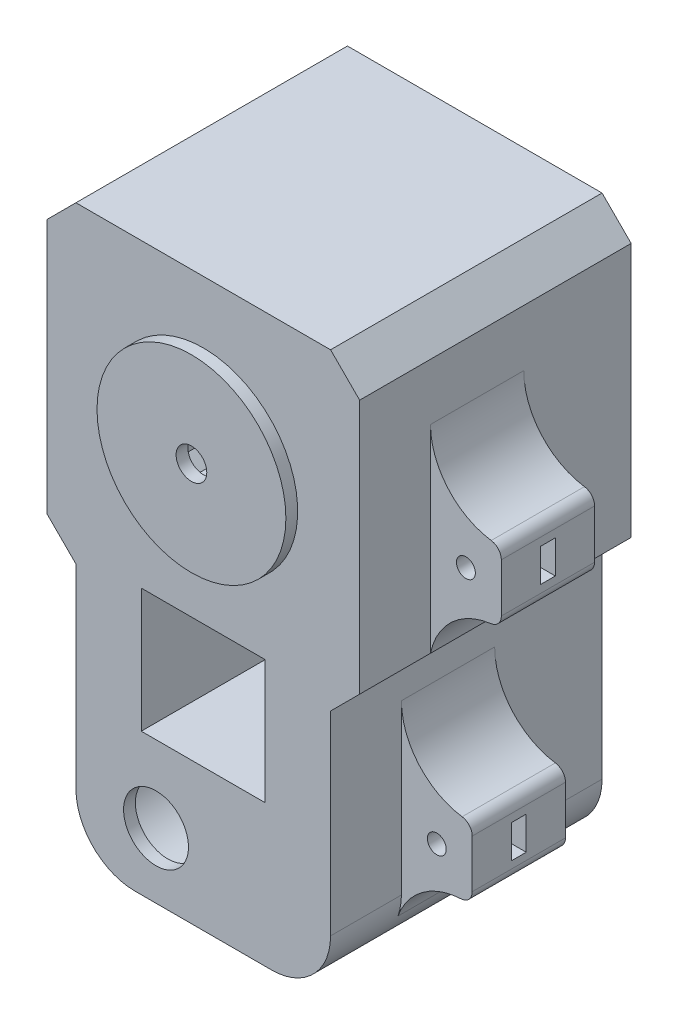
SolidWorks part; units mm, degrees
ref_plane "Alzado" through (0, 0, 0) normal (0, 0, 1) x (1, 0, 0)
ref_plane "Planta" through (0, 0, 0) normal (0, 1, 0) x (1, 0, 0)
ref_plane "Vista lateral" through (0, 0, 0) normal (1, 0, 0) x (0, 0, -1)
sketch "Croquis1" plane through (0, 0, 0) normal (0, 0, 1) x (1, 0, 0)
  line L0 (-19.5, -21.5) -> (-21.5, -19.5)
  line L1 (19.5, -21.5) -> (-19.5, -21.5)
  line L2 (21.5, -19.5) -> (21.5, 19.5)
  line L3 (19.5, 21.5) -> (-19.5, 21.5)
  line L4 (-21.5, -19.5) -> (-21.5, 19.5)
  line L5 (21.5, -21.5) -> (-21.5, 21.5) construction
  line L6 (21.5, 21.5) -> (-21.5, -21.5) construction
  line L7 (-19.5, 21.5) -> (-21.5, 19.5)
  line L8 (21.5, 19.5) -> (19.5, 21.5)
  line L9 (21.5, -19.5) -> (19.5, -21.5)
  line L10 (26.5, -21.5711) -> (26.5, 21.5711)
  line L11 (26.5, 21.5711) -> (21.5711, 26.5)
  line L12 (21.5711, 26.5) -> (-21.5711, 26.5)
  line L13 (-21.5711, 26.5) -> (-26.5, 21.5711)
  line L14 (-26.5, -21.5711) -> (-26.5, 21.5711)
  line L15 (-21.5711, -26.5) -> (-26.5, -21.5711)
  line L16 (21.5711, -26.5) -> (-21.5711, -26.5)
  line L17 (26.5, -21.5711) -> (21.5711, -26.5)
  point P0 (0, 0)
  dimension "D1" = 43
  dimension "D2" = 43
  dimension "D3" = 5
extrude "Saliente-Extruir1" add sketch "Croquis1" along normal mid plane 44
sketch "Croquis2" plane through (0, -26.5, 0) normal (0, -1, 0) x (1, 0, 0)
  line L4 (-21.5711, -22) -> (21.5711, -22)
  line L5 (21.5711, -22) -> (21.5711, 22)
  line L6 (21.5711, 22) -> (-21.5711, 22)
  line L7 (-21.5711, 22) -> (-21.5711, -22)
  line L8 (-21.5711, -22) -> (21.5711, -22)
  line L9 (21.5711, -22) -> (21.5711, 22)
  line L10 (21.5711, 22) -> (-21.5711, 22)
  line L11 (-21.5711, 22) -> (-21.5711, -22)
  dimension "D1" = 0
extrude "Saliente-Extruir2" add sketch "Croquis2" along normal blind 8
sketch "Croquis3" plane through (0, 0, 0) normal (0, 0, 1) x (1, 0, 0)
  line L0 (-19.5, -21.5) -> (19.5, -21.5) construction
  line L1 (-16.8806, -21.5) -> (16.8806, -21.5)
  line L2 (-16.8806, -21.5) -> (-16.8806, -29.5)
  line L3 (-16.8806, -29.5) -> (16.8806, -29.5)
  line L4 (16.8806, -21.5) -> (16.8806, -29.5)
  line L5 (0, 18.4155) -> (0, -35.026) construction
  dimension "D1" = 33.7612
  dimension "D2" = 8
extrude "Cortar-Extruir1" cut sketch "Croquis3" against normal through all contours L2 L1 L4 L3
sketch "Croquis4" plane through (0, 0, 22) normal (0, 0, -1) x (-1, 0, 0)
  line L10 (-26.5, -21.5711) -> (-21.5711, -26.5)
  line L11 (-21.5711, -26.5) -> (-21.5711, -34.5)
  line L12 (-21.5711, -34.5) -> (21.5711, -34.5)
  line L13 (21.5711, -34.5) -> (21.5711, -26.5)
  line L14 (21.5711, -26.5) -> (26.5, -21.5711)
  line L15 (26.5, -21.5711) -> (26.5, 21.5711)
  line L16 (26.5, 21.5711) -> (21.5711, 26.5)
  line L17 (21.5711, 26.5) -> (-21.5711, 26.5)
  line L18 (-21.5711, 26.5) -> (-26.5, 21.5711)
  line L19 (-26.5, 21.5711) -> (-26.5, -21.5711)
  line L20 (-26.5, -21.5711) -> (-21.5711, -26.5)
  line L21 (-21.5711, -26.5) -> (-21.5711, -34.5)
  line L22 (-21.5711, -34.5) -> (21.5711, -34.5)
  line L23 (21.5711, -34.5) -> (21.5711, -26.5)
  line L24 (21.5711, -26.5) -> (26.5, -21.5711)
  line L25 (26.5, -21.5711) -> (26.5, 21.5711)
  line L26 (26.5, 21.5711) -> (21.5711, 26.5)
  line L27 (21.5711, 26.5) -> (-21.5711, 26.5)
  line L28 (-21.5711, 26.5) -> (-26.5, 21.5711)
  line L29 (-26.5, 21.5711) -> (-26.5, -21.5711)
  circle A0 centre (0, 0) radius 11
  dimension "D2" = 22
  dimension "D1" = 0
extrude "Saliente-Extruir4" add sketch "Croquis4" against normal blind 2
sketch "Croquis7" plane through (0, 0, 24) normal (0, 0, 1) x (1, 0, 0)
  circle A0 centre (0, 0) radius 2.6
  circle A3 centre (0, 0) radius 16
  circle A4 centre (0, 0) radius 16
  dimension "D2" = 5.2
  dimension "D1" = 5
extrude "Saliente-Extruir5" add sketch "Croquis7" along normal blind 2
sketch "Croquis6" plane through (0, -29.5, 0) normal (0, 1, 0) x (1, 0, 0)
  line L0 (0, -24.5904) -> (0, 23.7869) construction
  line L1 (-14, 18) -> (14, 18)
  line L2 (-14, 18) -> (-14, 6)
  line L3 (-14, 6) -> (14, 6)
  line L4 (14, 18) -> (14, 6)
  dimension "D1" = 28
  dimension "D2" = 12
  dimension "D3" = 18
extrude "Cortar-Extruir3" cut sketch "Croquis6" against normal blind 13
sketch "Croquis8" plane through (0, 0, 0) normal (0, 0, 1) x (1, 0, 0)
  line L0 (-26.5, -21.5711) -> (-26.5, 21.5711)
  line L1 (-26.5, -21.5711) -> (-26.5, 21.5711)
  line L2 (-26.5, 21.5711) -> (-21.5711, 26.5)
  line L3 (-26.5, 21.5711) -> (-21.5711, 26.5)
  line L4 (-21.5711, 26.5) -> (21.5711, 26.5)
  line L5 (-21.5711, 26.5) -> (21.5711, 26.5)
  line L6 (21.5711, 26.5) -> (26.5, 21.5711)
  line L7 (21.5711, 26.5) -> (26.5, 21.5711)
  line L8 (26.5, 21.5711) -> (26.5, -21.5711)
  line L9 (26.5, 21.5711) -> (26.5, -21.5711)
  line L10 (26.5, -21.5711) -> (21.5711, -26.5)
  line L11 (26.5, -21.5711) -> (21.5711, -26.5)
  line L12 (21.5711, -26.5) -> (21.5711, -34.5)
  line L13 (21.5711, -26.5) -> (21.5711, -34.5)
  line L14 (21.5711, -34.5) -> (-21.5711, -34.5)
  line L15 (21.5711, -34.5) -> (-21.5711, -34.5)
  line L16 (-21.5711, -34.5) -> (-21.5711, -26.5)
  line L17 (-21.5711, -34.5) -> (-21.5711, -26.5)
  line L18 (-21.5711, -26.5) -> (-26.5, -21.5711)
  line L19 (-21.5711, -26.5) -> (-26.5, -21.5711)
  line L20 (0, 0) -> (-39.949, 0) construction
  line L21 (0, 0) -> (0, 31.7363) construction
  line L22 (26.5, -12) -> (38.5, -12)
  line L23 (-26.5, 0) -> (-38.5, 0)
  line L24 (-26.5, 0) -> (-26.5, -12)
  line L25 (-26.5, -12) -> (-38.5, -12)
  line L26 (-38.5, 0) -> (-38.5, -12)
  line L27 (38.5, 0) -> (38.5, -12)
  line L28 (26.5, 0) -> (38.5, 0)
  line L29 (26.5, 0) -> (26.5, -12)
  line L30 (-38.5, -12) -> (-26.5, 0) construction
  circle A0 centre (-32.5, -6) radius 1.6
  circle A1 centre (32.5, -6) radius 1.6
  dimension "D3" = 3.2
  dimension "D1" = 12
  dimension "D2" = 12
extrude "Saliente-Extruir6" add sketch "Croquis8" along normal blind 12 and the other way blind 3.8 contours L23 L26 L25 L1 | L28 L9 L22 L27 region at (-32.5, -11.8303, 0) region at (26.6697, -6, 0)
sketch "Croquis9" plane through (38.5, 0, 0) normal (1, 0, 0) x (0, 0, -1)
  line L0 (3.8, -6) -> (-12, -6) construction
  line L1 (3.8, 0) -> (3.8, -12) construction
  line L2 (-12, 0) -> (-12, -12) construction
  line L4 (-2.85, -3.2) -> (-5.35, -3.2)
  line L5 (-2.85, -3.2) -> (-2.85, -8.8)
  line L6 (-2.85, -8.8) -> (-5.35, -8.8)
  line L7 (-5.35, -3.2) -> (-5.35, -8.8)
  line L8 (-2.85, -3.2) -> (-5.35, -8.8) construction
  line L9 (-2.85, -8.8) -> (-5.35, -3.2) construction
  point P6 (-4.1, -6)
  dimension "D1" = 5.6
  dimension "D2" = 2.5
extrude "Cortar-Extruir4" cut sketch "Croquis9" against normal blind 10
mirror "Simetría1" about plane through (0, 0, 0) normal (1, 0, 0) of "Cortar-Extruir4"
sketch "Croquis11" plane through (0, -34.5, 0) normal (0, -1, 0) x (1, 0, 0)
  line L4 (-21.5711, 24) -> (-21.5711, -22)
  line L5 (-21.5711, -22) -> (21.5711, -22)
  line L6 (21.5711, -22) -> (21.5711, 24)
  line L7 (21.5711, 24) -> (-21.5711, 24)
  line L8 (-21.5711, 24) -> (-21.5711, -22)
  line L9 (-21.5711, -22) -> (21.5711, -22)
  line L10 (21.5711, -22) -> (21.5711, 24)
  line L11 (21.5711, 24) -> (-21.5711, 24)
  dimension "D1" = 0
extrude "Saliente-Extruir8" add sketch "Croquis11" along normal blind 35
sketch "Croquis12" plane through (0, 0, -22) normal (0, 0, -1) x (-1, 0, 0)
  line L0 (0, 0) -> (0, -75.996) construction
  line L1 (18.5711, -66.5) -> (-18.5711, -66.5)
  line L2 (18.5711, -66.5) -> (18.5711, -38.5)
  line L3 (18.5711, -38.5) -> (-18.5711, -38.5)
  line L4 (-18.5711, -66.5) -> (-18.5711, -38.5)
  line L5 (21.5711, -69.5) -> (21.5711, -26.5) construction
  line L6 (21.5711, -69.5) -> (-21.5711, -69.5) construction
  dimension "D1" = 3
  dimension "D2" = 3
  dimension "D3" = 28
extrude "Cortar-Extruir5" cut sketch "Croquis12" against normal offset from surface (44 mm away) 2 up to face at (-16, 0, 24)
sketch "Croquis14" plane through (0, 0, 24) normal (0, 0, 1) x (1, 0, 0)
  line L0 (0, 0) -> (0, -70.2297) construction
  line L1 (10.5, -24.5) -> (-10.5, -24.5)
  line L2 (10.5, -24.5) -> (10.5, -45.5)
  line L3 (10.5, -45.5) -> (-10.5, -45.5)
  line L4 (-10.5, -24.5) -> (-10.5, -45.5)
  line L5 (10.5, -24.5) -> (-10.5, -45.5) construction
  line L6 (10.5, -45.5) -> (-10.5, -24.5) construction
  point P0 (0, -35)
  dimension "D1" = 35
  dimension "D2" = 21
  dimension "D3" = 21
extrude "Cortar-Extruir7" cut sketch "Croquis14" against normal blind 25
sketch "Croquis15" plane through (0, 0, 22) normal (0, 0, -1) x (-1, 0, 0)
  line L0 (-10.5, -38.5) -> (-18.5711, -38.5)
  line L1 (-18.5711, -38.5) -> (-18.5711, -49.5)
  line L2 (-18.5711, -49.5) -> (18.5711, -49.5)
  line L3 (18.5711, -49.5) -> (18.5711, -38.5)
  line L4 (18.5711, -38.5) -> (10.5, -38.5)
  line L5 (10.5, -38.5) -> (10.5, -45.5)
  line L6 (10.5, -45.5) -> (-10.5, -45.5)
  line L7 (-10.5, -45.5) -> (-10.5, -38.5)
  dimension "D1" = 4
  dimension "D2" = 90
  dimension "D3" = 90
extrude "Saliente-Extruir9" add sketch "Croquis15" along normal blind 25
sketch "Croquis16" plane through (0, 0, -3) normal (0, 0, -1) x (-1, 0, 0)
  line L1 (-10.5, -45.5) -> (10.5, -45.5)
  line L2 (-10.5, -45.5) -> (-10.5, -24.5)
  line L3 (-10.5, -24.5) -> (10.5, -24.5)
  line L4 (10.5, -45.5) -> (10.5, -24.5)
extrude "Saliente-Extruir11" add sketch "Croquis16" against normal blind 3.2
sketch "Croquis17" plane through (0, -49.5, 0) normal (0, -1, 0) x (1, 0, 0)
  line L0 (0, -10) -> (0, 26) construction
  line L1 (16, 26) -> (-16, 26) construction
  circle A0 centre (0, 8) radius 1.6
  point P6 (0, 0)
  dimension "D1" = 3.2
  dimension "D2" = 8
extrude "Cortar-Extruir8" cut sketch "Croquis17" against normal blind 40
sketch "Croquis18" plane through (0, -21.5, 0) normal (0, 1, 0) x (1, 0, 0)
  circle A0 centre (0, -8) radius 1.6 construction
  circle A1 centre (0, -8) radius 1.6
  circle A2 centre (0, -8) radius 4.8
  dimension "D1" = 3.2
extrude "Cortar-Extruir9" cut sketch "Croquis18" against normal blind 2
sketch "Croquis13" plane through (0, 0, 22) normal (0, 0, -1) x (-1, 0, 0)
  line L0 (18.5711, -52.5) -> (-18.5711, -52.5) construction
  line L1 (18.5711, -66.5) -> (18.5711, -38.5) construction
  line L2 (-18.5711, -38.5) -> (-18.5711, -66.5) construction
  line L3 (0, 0) -> (0, -68.0761) construction
  circle A0 centre (8, -58.5) radius 5.5
  point P8 (0, 0)
  point P9 (-8.0054, -58.5)
  point P13 (10.141, -58.5)
  dimension "D1" = 11
  dimension "D3" = 11
  dimension "D2" = 6
  dimension "D4" = 8
extrude "Cortar-Extruir6" cut sketch "Croquis13" against normal blind 2
fillet "Redondeo1" radius 10 2 edges at (-18.5711, -66.5, 0) (18.5711, -66.5, 0)
fillet "Redondeo2" radius 10 2 edges at (-21.5711, -69.5, 1) (21.5711, -69.5, 1)
sketch "Croquis19" plane through (21.5711, 0, 0) normal (1, 0, 0) x (0, 0, -1)
  line L0 (0, 0) -> (0, -69.5) construction
  line L1 (22, -69.5) -> (-24, -69.5) construction
  line L2 (3.8, 0) -> (3.8, -12) construction
  line L3 (3.8, -55) -> (-12, -55)
  line L4 (3.8, -55) -> (3.8, -43)
  line L5 (3.8, -43) -> (-12, -43)
  line L6 (-12, -55) -> (-12, -43)
  line L7 (-12, 0) -> (-12, -12) construction
  line L8 (-2.85, -8.8) -> (-2.85, -3.2) construction
  line L9 (-2.85, -51.8) -> (-5.35, -51.8)
  line L10 (-2.85, -51.8) -> (-2.85, -46.2)
  line L11 (-2.85, -46.2) -> (-5.35, -46.2)
  line L12 (-5.35, -51.8) -> (-5.35, -46.2)
  line L13 (-5.35, -3.2) -> (-5.35, -8.8) construction
  line L14 (3.8, -49) -> (-12, -49) construction
  dimension "D1" = 12
  dimension "D2" = 43
  dimension "D3" = 5.6
extrude "Saliente-Extruir12" add sketch "Croquis19" along normal blind 12
sketch "Croquis20" plane through (0, 0, -3.8) normal (0, 0, -1) x (-1, 0, 0)
  line L0 (-33.5711, -49) -> (-21.5711, -49) construction
  line L1 (-33.5711, -55) -> (-33.5711, -43) construction
  line L2 (-21.5711, -59.5) -> (-21.5711, -26.5) construction
  line L3 (-27.5711, -55) -> (-27.5711, -43) construction
  line L4 (-33.5711, -55) -> (-21.5711, -55) construction
  line L5 (-33.5711, -43) -> (-21.5711, -43) construction
  circle A0 centre (-27.5711, -49) radius 1.6
  dimension "D1" = 3.2
extrude "Cortar-Extruir10" cut sketch "Croquis20" against normal through all
mirror "Simetría2" about plane through (0, 0, 0) normal (1, 0, 0) of "Saliente-Extruir12", "Cortar-Extruir10"
fillet "Redondeo3" radius 12 4 edges at (21.5711, -55, 4.1) (26.5, -12, 4.1) (26.5, 0, 4.1) (21.5711, -43, 4.1)
fillet "Redondeo4" radius 2 4 edges at (33.5711, -55, 4.1) (33.5711, -43, 4.1) (38.5, -12, 4.1) (38.5, 0, 4.1)
fillet "Redondeo5" radius 10 4 edges at (-21.5711, -55, 4.1) (-21.5711, -43, 4.1) (-26.5, -12, 4.1) (-26.5, 0, 4.1)
fillet "Redondeo6" radius 2 4 edges at (-33.5711, -43, 4.1) (-38.5, 0, 4.1) (-38.5, -12, 4.1) (-33.5711, -55, 4.1)
